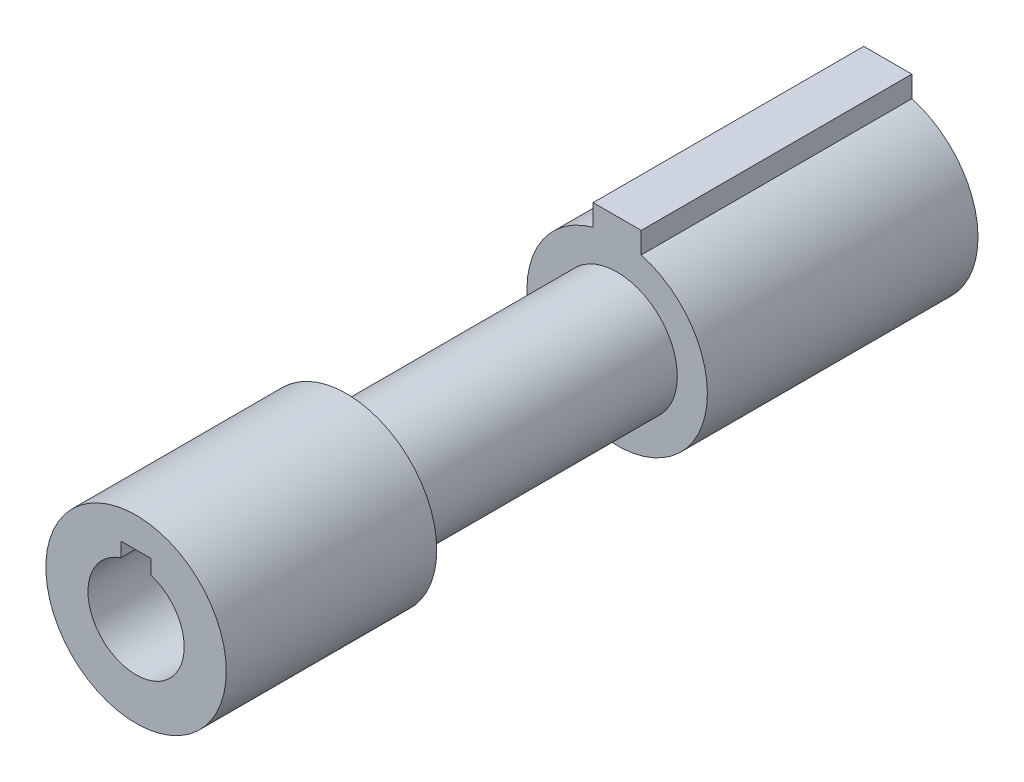
SolidWorks part; units mm, degrees
ref_plane "Front Plane" through (0, 0, 0) normal (0, 0, 1) x (1, 0, 0)
ref_plane "Top Plane" through (0, 0, 0) normal (0, 1, 0) x (1, 0, 0)
ref_plane "Right Plane" through (0, 0, 0) normal (1, 0, 0) x (0, 0, -1)
sketch "Sketch1" plane through (0, 0, 0) normal (0, 0, 1) x (1, 0, 0)
  line L1 (2.5, 10) -> (-2.5, 10)
  line L2 (2.5, 10) -> (2.5, 6)
  line L3 (2.5, 6) -> (-2.5, 6)
  line L4 (-2.5, 10) -> (-2.5, 6)
  line L5 (2.5, 10) -> (-2.5, 6) construction
  line L6 (2.5, 6) -> (-2.5, 10) construction
  circle A0 centre (0, 0) radius 15
  circle A1 centre (0, 0) radius 34.5
  circle A2 centre (0, 0) radius 8
  point P5 (0, 8)
  dimension "D1" = 69
  dimension "D4" = 16
  dimension "D5" = 30
  dimension "D2" = 5
  dimension "D3" = 4
extrude "Boss-Extrude1" add sketch "Sketch1" along normal blind 35 contours A0 A2 L4 L1 L2 region at (-14.5757, 0, 0)
sketch "Sketch2" plane through (0, 0, 0) normal (0, 0, 1) x (1, 0, 0)
  circle A0 centre (0, 0) radius 10
  dimension "D1" = 20
extrude "Boss-Extrude3" add sketch "Sketch1<6>" along normal blind 1 contours A2 L2 L1 L4 region at (0, 8.9306, 0)
sketch "Sketch1<6>" plane through (0, 0, 0) normal (0, 0, 1) x (1, 0, 0) same geometry as "Sketch1"
extrude "Boss-Extrude4" add sketch "Sketch2" against normal blind 50
ref_plane "Plane1" through (0, 0, -50) normal (0, 0, -1) x (-1, 0, 0)
sketch "Sketch3" plane through (0, 0, -50) normal (0, 0, -1) x (-1, 0, 0)
  line L1 (-4, 18) -> (4, 18)
  line L2 (-4, 18) -> (-4, -18)
  line L3 (-4, -18) -> (4, -18)
  line L4 (4, 18) -> (4, -18)
  line L5 (-4, 18) -> (4, -18) construction
  line L6 (-4, -18) -> (4, 18) construction
  circle A0 centre (0, 0) radius 15
  dimension "D1" = 30
  dimension "D2" = 36
  dimension "D3" = 8
extrude "Boss-Extrude5" add sketch "Sketch3" along normal blind 40 and the other way blind 5 contours L4 A0 | L2 A0 | L4 A0 L2 | A0 L4 L1 L2 region at (0, 16.406, -50) region at (0, 0, -50) region at (8.5764, 0, -50) region at (-8.5764, 0, -50)
sketch "Sketch4" plane through (0, 0, -50) normal (0, 0, -1) x (-1, 0, 0)
  circle A0 centre (0, 0) radius 10
  dimension "D1" = 20
extrude "Cut-Extrude2" cut sketch "Sketch4" along normal blind 30 contours A0 region at (0, 0, -50)
